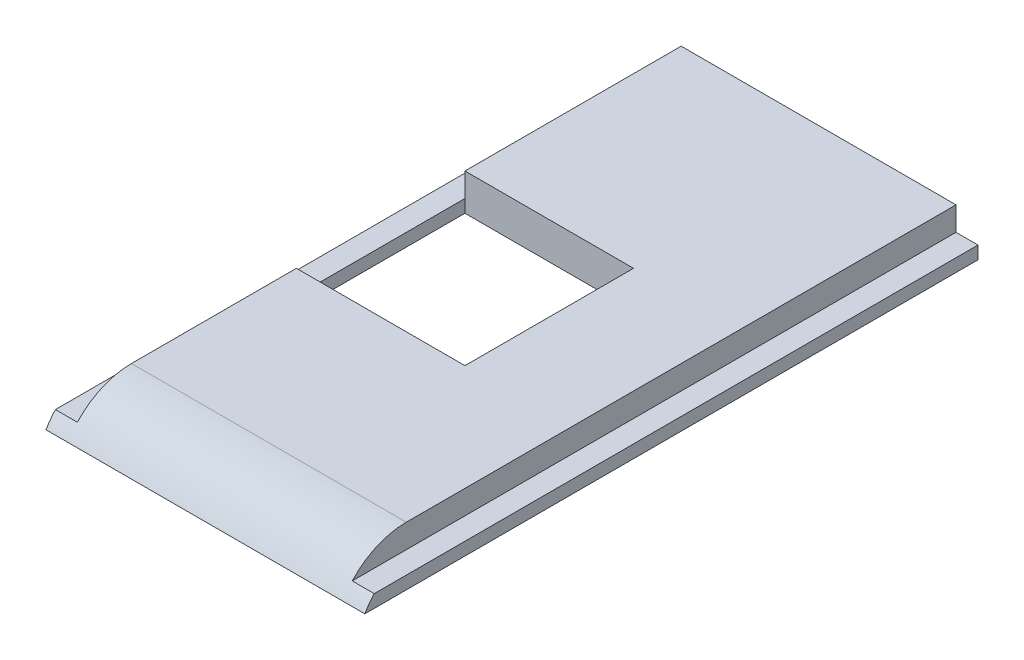
SolidWorks part; units mm, degrees
ref_plane "Přední rovina" through (0, 0, 0) normal (0, 0, 1) x (1, 0, 0)
ref_plane "Horní rovina" through (0, 0, 0) normal (0, 1, 0) x (1, 0, 0)
ref_plane "Pravá rovina" through (0, 0, 0) normal (1, 0, 0) x (0, 0, -1)
sketch "Skica1" plane through (0, 0, 0) normal (0, 1, 0) x (1, 0, 0)
  line L5 (0, 0) -> (17.4, 0)
  line L6 (0, 0) -> (0, 27)
  line L7 (0, 27) -> (17.4, 27)
  line L8 (17.4, 0) -> (17.4, 27)
  dimension "D1" = 27
  dimension "D2" = 17.4
extrude "Přidat vysunutím1" add sketch "Skica1" along normal blind 2
sketch "Skica2" plane through (0, 0, 0) normal (0, -1, 0) x (1, 0, 0)
  line L1 (0, 0) -> (17.4, 0)
  line L2 (0, 0) -> (0, -27)
  line L3 (0, -27) -> (17.4, -27)
  line L4 (17.4, 0) -> (17.4, -27)
extrude "Přidat vysunutím2" add sketch "Skica2" along normal blind 6
fillet "Zaoblit1" radius 4 1 edges at (8.7, 2, 0)
sketch "Skica3" plane through (0, -6, 0) normal (0, -1, 0) x (1, 0, 0)
  line L1 (0, 0) -> (17.4, 0)
  line L2 (0, 0) -> (0, -27)
  line L3 (0, -27) -> (17.4, -27)
  line L4 (17.4, 0) -> (17.4, -27)
extrude "Odebrat vysunutím1" cut sketch "Skica3" against normal blind 6
sketch "Skica4" plane through (0, 2, 0) normal (0, 1, 0) x (1, 0, 0)
  line L0 (0, 0.5359) -> (17.4, 0.5359) construction
  line L1 (0, 27) -> (1.2, 27)
  line L2 (0, 27) -> (0, 0.5359)
  line L3 (0, 0.5359) -> (1.2, 0.5359)
  line L4 (1.2, 27) -> (1.2, 0.5359)
  line L6 (17.4, 27) -> (16.2, 27)
  line L7 (17.4, 27) -> (17.4, 0.5359)
  line L8 (17.4, 0.5359) -> (16.2, 0.5359)
  line L9 (16.2, 27) -> (16.2, 0.5359)
  dimension "D1" = 1.2
  dimension "D2" = 1.2
extrude "Odebrat vysunutím2" cut sketch "Skica4" against normal blind 1.2
sketch "Skica7" plane through (0, 0, -27) normal (0, 0, -1) x (-1, 0, 0)
  line L1 (-16.2, 2) -> (-1.2, 2)
  line L2 (-16.2, 2) -> (-16.2, 0.8)
  line L3 (-16.2, 0.8) -> (-1.2, 0.8)
  line L4 (-1.2, 2) -> (-1.2, 0.8)
  line L5 (-17.4, 0.8) -> (0, 0.8)
  line L6 (-17.4, 0.8) -> (-17.4, 0)
  line L7 (-17.4, 0) -> (0, 0)
  line L8 (0, 0.8) -> (0, 0)
extrude "Přidat vysunutím3" add sketch "Skica7" along normal blind 7 contours L3 L4 L1 L2 | L7 L8 L5 L6
sketch "Skica8" plane through (0, 2, 0) normal (0, 1, 0) x (1, 0, 0)
  line L0 (1.2, 34) -> (1.2, 4) construction
  line L1 (1.2, 22.2) -> (10.4, 22.2)
  line L2 (1.2, 22.2) -> (1.2, 13)
  line L3 (1.2, 13) -> (10.4, 13)
  line L4 (10.4, 22.2) -> (10.4, 13)
  line L5 (16.2, 34) -> (1.2, 34) construction
  dimension "D1" = 9.2
  dimension "D2" = 21
extrude "Odebrat vysunutím5" cut sketch "Skica8" against normal blind 7
sketch "Skica9" plane through (0, 2, 0) normal (0, 1, 0) x (1, 0, 0)
  line L0 (0, 0.5359) -> (17.4, 0.5359) construction
  line L1 (0, 34) -> (1.2, 34)
  line L2 (0, 34) -> (0, 0.5359)
  line L3 (0, 0.5359) -> (1.2, 0.5359)
  line L4 (1.2, 34) -> (1.2, 0.5359)
  line L6 (16.2, 34) -> (17.4, 34)
  line L7 (16.2, 34) -> (16.2, 0.5359)
  line L8 (16.2, 0.5359) -> (17.4, 0.5359)
  line L9 (17.4, 34) -> (17.4, 0.5359)
  dimension "D1" = 15
extrude "Odebrat vysunutím6" cut sketch "Skica9" against normal blind 1.3
